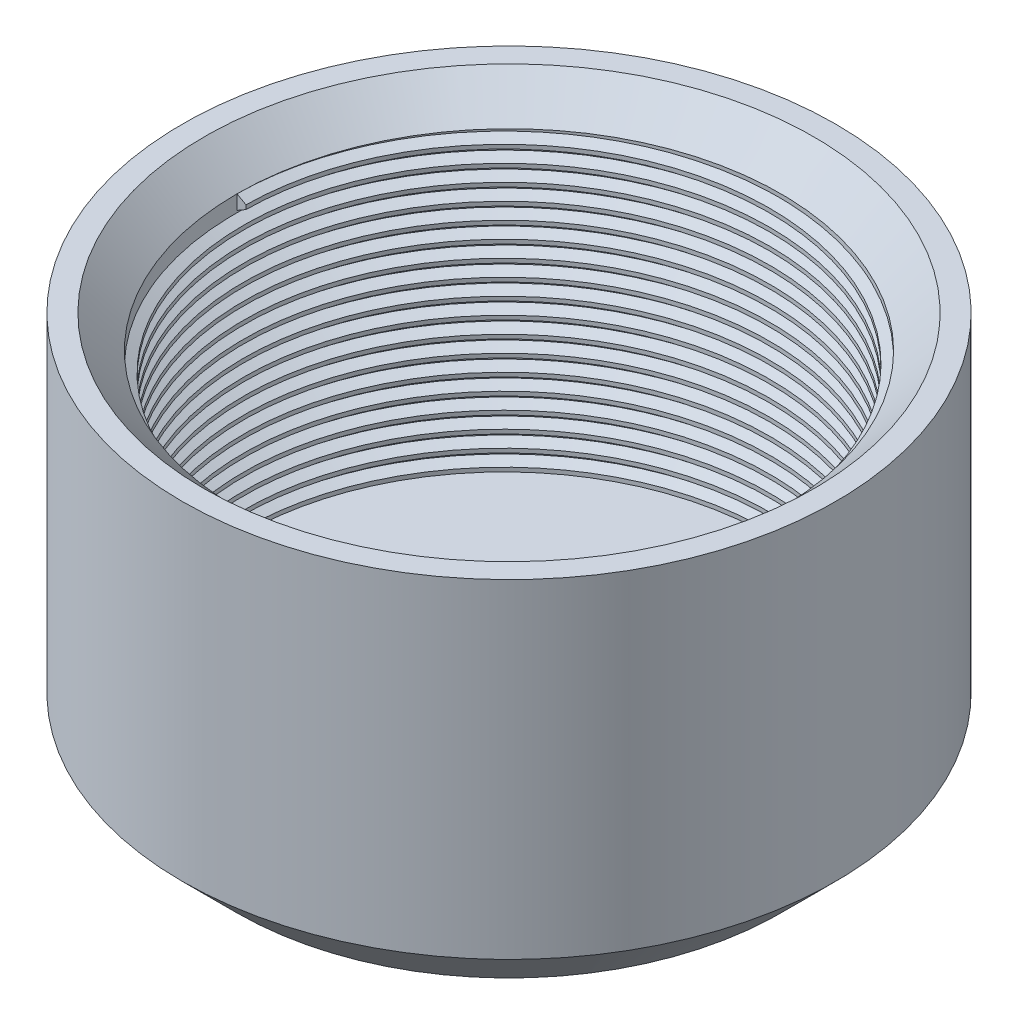
SolidWorks part; units mm, degrees
ref_plane "Front Plane" through (0, 0, 0) normal (0, 0, 1) x (1, 0, 0)
ref_plane "Top Plane" through (0, 0, 0) normal (0, 1, 0) x (1, 0, 0)
ref_plane "Right Plane" through (0, 0, 0) normal (1, 0, 0) x (0, 0, -1)
sketch "Sketch1" plane through (0, 0, 0) normal (0, 1, 0) x (1, 0, 0)
  circle A0 centre (0, 0) radius 24.8
  circle A1 centre (0, 0) radius 29.8
  dimension "D1" = 5
extrude "Boss-Extrude1" add sketch "Sketch1" along normal blind 30
chamfer "Chamfer4" distance 3 angle 45 1 edges at (0, 30, 24.8)
thread "Thread2" pitch 1.5 method extrude profile "Thread Profile2" start angle 0, offset 0, length 30, pitch 1.5, diameter 49.6
ref_plane "Plane2" through (-24.8, 27, 0) normal (0, 0, 1) x (-1, 0, 0)
sketch "Thread Profile2" plane through (-24.8, 27, 0) normal (0, 0, 1) x (-1, 0, 0)
  line L0 (0, 0) -> (0, 1.5) construction
  line L11 (0, 0) -> (0, 1.3125)
  line L12 (0, 1.3125) -> (-0.8119, 0.8437)
  line L13 (-0.8119, 0.8437) -> (-0.8119, 0.4687)
  line L15 (-0.8119, 0.4687) -> (0, 0)
  line L17 (-0.8119, 0.6562) -> (0, 0.6562) construction
  point P2 (0, 0)
  dimension "Pitch" = 1.5
  dimension "Profile_Angle" = 60
  dimension "Profile_Land" = 0.375
  dimension "Profile_Height" = 0.8119
sketch "Sketch2" plane through (0, 0, 0) normal (0, -1, 0) x (1, 0, 0)
  circle A1 centre (0, 0) radius 29.8
  circle A2 centre (0, 0) radius 29.8
  dimension "D1" = 0
extrude "Boss-Extrude2" add sketch "Sketch2" along normal blind 5
chamfer "Chamfer1" distance 5 angle 45 1 edges at (0, -5, -29.8)
sketch "Sketch3" plane through (0, -5, 0) normal (0, -1, 0) x (1, 0, 0)
  line L0 (0, 11.7484) -> (0, 13.8393)
  line L1 (-1.0944, 13.8393) -> (1.0944, 13.8393)
  line L2 (1.0944, 13.8393) -> (1.6933, 11.6257)
  line L3 (-11.6257, -1.6933) -> (-2.2323, -1.6933)
  line L4 (11.6257, 1.6933) -> (1.9007, 1.6933)
  line L5 (-1.0944, 13.8393) -> (-1.6933, 11.6257)
  line L6 (7.8674, 11.438) -> (7.2793, 9.2215)
  line L7 (5.9719, 12.5324) -> (4.3464, 10.9148)
  line L8 (5.9719, 12.5324) -> (7.8674, 11.438)
  line L9 (12.5324, 5.9719) -> (10.9148, 4.3464)
  line L10 (11.438, 7.8674) -> (9.2215, 7.2793)
  line L11 (11.438, 7.8674) -> (12.5324, 5.9719)
  line L12 (13.8393, -1.0944) -> (11.6257, -1.6933)
  line L13 (13.8393, 1.0944) -> (11.6257, 1.6933)
  line L14 (13.8393, 1.0944) -> (13.8393, -1.0944)
  line L15 (11.438, -7.8674) -> (9.2215, -7.2793)
  line L16 (12.5324, -5.9719) -> (10.9148, -4.3464)
  line L17 (12.5324, -5.9719) -> (11.438, -7.8674)
  line L18 (5.9719, -12.5324) -> (4.3464, -10.9148)
  line L19 (7.8674, -11.438) -> (7.2793, -9.2215)
  line L20 (7.8674, -11.438) -> (5.9719, -12.5324)
  line L21 (-1.0944, -13.8393) -> (-1.6933, -11.6257)
  line L22 (1.0944, -13.8393) -> (1.6933, -11.6257)
  line L23 (1.0944, -13.8393) -> (-1.0944, -13.8393)
  line L24 (-7.8674, -11.438) -> (-7.2793, -9.2215)
  line L25 (-5.9719, -12.5324) -> (-4.3464, -10.9148)
  line L26 (-5.9719, -12.5324) -> (-7.8674, -11.438)
  line L27 (-12.5324, -5.9719) -> (-10.9148, -4.3464)
  line L28 (-11.438, -7.8674) -> (-9.2215, -7.2793)
  line L29 (-11.438, -7.8674) -> (-12.5324, -5.9719)
  line L30 (-13.8393, 1.0944) -> (-11.6257, 1.6933)
  line L31 (-13.8393, -1.0944) -> (-11.6257, -1.6933)
  line L32 (-13.8393, -1.0944) -> (-13.8393, 1.0944)
  line L33 (-11.438, 7.8674) -> (-9.2215, 7.2793)
  line L34 (-12.5324, 5.9719) -> (-10.9148, 4.3464)
  line L35 (-12.5324, 5.9719) -> (-11.438, 7.8674)
  line L36 (-5.9719, 12.5324) -> (-4.3464, 10.9148)
  line L37 (-7.8674, 11.438) -> (-7.2793, 9.2215)
  line L38 (-7.8674, 11.438) -> (-5.9719, 12.5324)
  line L39 (-10.9148, -4.3464) -> (-7.4075, -3.3987)
  line L40 (10.9148, 4.3464) -> (7.3973, 3.4209)
  line L41 (-0.2932, 1.6933) -> (-2.2323, -1.6933)
  line L42 (1.9007, 1.6933) -> (-0.0593, -1.6933)
  line L43 (-0.2932, 1.6933) -> (-7.9722, 1.6933)
  line L44 (-0.0593, -1.6933) -> (7.9722, -1.6933)
  arc A0 (-7.4075, -3.3987) -> (7.9722, -1.6933) centre (0, 0) ccw
  arc A1 (-9.2215, -7.2793) -> (-7.2793, -9.2215) centre (0, 0) ccw
  arc A2 (7.3973, 3.4209) -> (-7.9722, 1.6933) centre (0, 0) ccw
  arc A3 (9.2215, 7.2793) -> (7.2793, 9.2215) centre (0, 0) ccw
  arc A4 (-4.3464, -10.9148) -> (-1.6933, -11.6257) centre (0, 0) ccw
  arc A5 (1.6933, -11.6257) -> (4.3464, -10.9148) centre (0, 0) ccw
  arc A6 (7.2793, -9.2215) -> (9.2215, -7.2793) centre (0, 0) ccw
  arc A7 (10.9148, -4.3464) -> (11.6257, -1.6933) centre (0, 0) ccw
  arc A8 (4.3464, 10.9148) -> (1.6933, 11.6257) centre (0, 0) ccw
  arc A9 (-1.6933, 11.6257) -> (-4.3464, 10.9148) centre (0, 0) ccw
  arc A10 (-7.2793, 9.2215) -> (-9.2215, 7.2793) centre (0, 0) ccw
  arc A11 (-10.9148, 4.3464) -> (-11.6257, 1.6933) centre (0, 0) ccw
  point P58 (0, 0)
extrude "Boss-Extrude3" add sketch "Sketch3" along normal blind 0.05 contours L34 A11 L30 L32 L31 L3 L41 L43 A2 L40 L9 L11 L10 A3 L6 L8 L7 A8 L2 L1 L5 A9 L36 L38 L37 A10 L33 L35 | L16 A7 L12 L14 L13 L4 L42 L44 A0 L39 L27 L29 L28 A1 L24 L26 L25 A4 L21 L23 L22 A5 L18 L20 L19 A6 L15 L17 region at (-0.5472, -5, 13.5332) region at (12.6526, -5, 1.0984)
